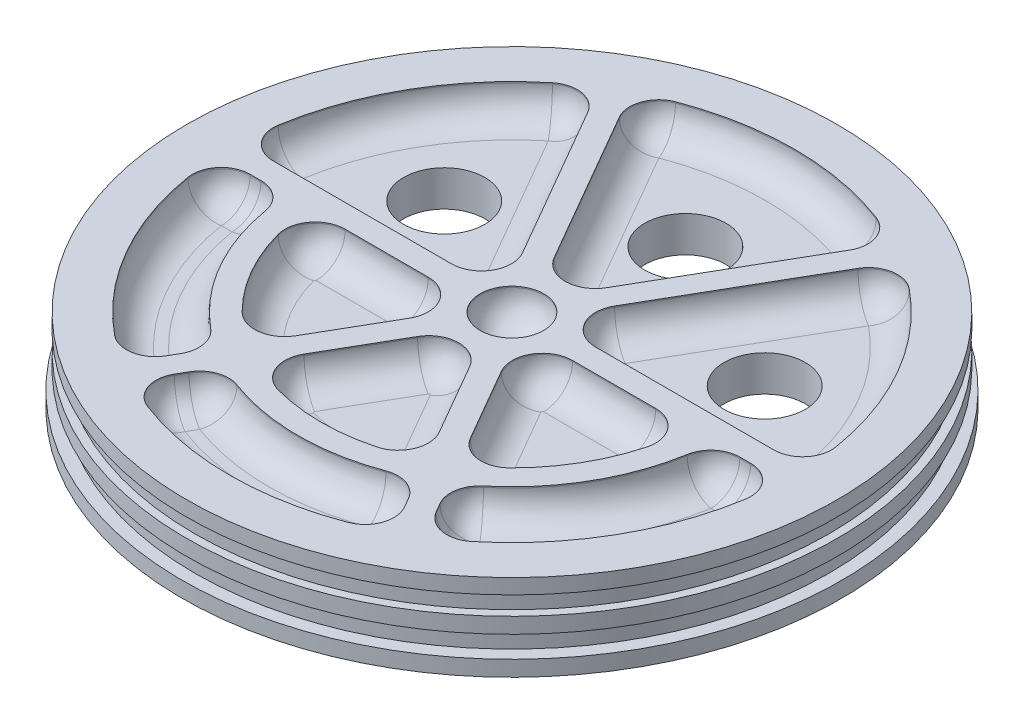
SolidWorks part; units mm, degrees
material "6061-T6 (SS)"
ref_plane "Front Plane" through (0, 0, 0) normal (0, 0, 1) x (1, 0, 0)
ref_plane "Top Plane" through (0, 0, 0) normal (0, 1, 0) x (1, 0, 0)
ref_plane "Right Plane" through (0, 0, 0) normal (1, 0, 0) x (0, 0, -1)
sketch "Sketch1" plane through (0, 0, 0) normal (0, 0, 1) x (1, 0, 0)
  line L0 (0, 48.1922) -> (0, -25.6743) construction
  line L1 (0, 0) -> (72.39, 0)
  line L2 (72.39, 0) -> (72.39, 3.429)
  line L3 (72.39, 3.429) -> (69.6468, 3.429)
  line L4 (69.6468, 3.429) -> (69.6468, 7.493)
  line L5 (69.6468, 7.493) -> (71.4248, 7.493)
  line L6 (71.4248, 7.493) -> (71.4248, 10.922)
  line L7 (71.4248, 10.922) -> (69.6468, 10.922)
  line L8 (62.0268, 18.288) -> (62.0268, 11.684)
  line L9 (62.0268, 11.684) -> (0, 11.684)
  line L10 (0, 11.684) -> (0, 0)
  line L11 (69.6468, 10.922) -> (69.6468, 14.986)
  line L12 (69.6468, 14.986) -> (71.4248, 14.986)
  line L13 (71.4248, 14.986) -> (71.4248, 18.288)
  line L14 (71.4248, 18.288) -> (62.0268, 18.288)
  dimension "D2" = 4.064
  dimension "D5" = 11.684
  dimension "D7" = 4.064
  dimension "D3" = 3.302
  dimension "D4" = 3.429
  dimension "D8" = 7.62
  dimension "D9" = 6.604
  dimension "D1" = 72.39
  dimension "D10" = 1.778
  dimension "D6" = 69.6468
revolve "Revolve1" add sketch "Sketch1" angle 360 about L0
sketch "Sketch6" plane through (0, 0, 0) normal (0, -1, 0) x (1, 0, 0)
  circle A0 centre (0, 0) radius 66.04
  dimension "D1" = 132.08
extrude "Boss-Extrude1" add sketch "Sketch6" along normal blind 2.54
fillet "CNC ID Fillet" [suppressed] radius 0.4064
fillet "CNC OD Fillet" [suppressed] radius 0.127
chamfer "CNC Chamfers" [suppressed] distance 0.508 angle 65
hole_wizard "Pipe Tap Drill for 1/2 Tap - Fill Valve" positions "Sketch13" profile "Sketch14" hole size "1/2" standard "ANSI Inch" end condition through all
sketch "Sketch13" plane through (0, -2.54, 0) normal (0, -1, 0) x (-1, 0, 0)
  point P4 (0, 38.1)
  dimension "D1" = 38.1
sketch "Sketch14" plane through (0, -2.54, -38.1) normal (1, 0, 0) x (0, 0, -1)
  line L0 (0, 0) -> (0, 20.828)
  line L1 (0, 20.828) -> (8.9281, 20.828)
  line L2 (8.9281, 20.828) -> (8.9281, 0)
  line L5 (8.9281, 0) -> (0, 0)
  line L11 (0, -6.35) -> (0, 107.95) construction
  dimension "Thru Hole Dia." = 17.8562
  dimension "Thru Hole Depth" = 20.828
hole_wizard "Pipe Tap Drill for 1/4 Tap - Solenoid Valve" positions "Sketch15" profile "Sketch16" hole size "1/2" standard "ANSI Inch" end condition through all
sketch "Sketch15" plane through (0, -2.54, 0) normal (0, -1, 0) x (-1, 0, 0)
  line L2 (-35.1953, 20.32) -> (0, 0) construction
  line L4 (0, 0) -> (0, 38.1) construction
  point P4 (-35.1953, 20.32)
  dimension "D1" = 60
  dimension "D2" = 40.64
sketch "Sketch16" plane through (35.1953, -2.54, -20.32) normal (1, 0, 0) x (0, 0, -1)
  line L0 (0, 0) -> (0, 20.828)
  line L1 (0, 20.828) -> (8.9281, 20.828)
  line L2 (8.9281, 20.828) -> (8.9281, 0)
  line L5 (8.9281, 0) -> (0, 0)
  line L11 (0, -6.35) -> (0, 107.95) construction
  dimension "Thru Hole Dia." = 17.8562
  dimension "Thru Hole Depth" = 20.828
hole_wizard "Pipe Tap Drill for 1/2 Tap - Cryo Valve" positions "Sketch17" profile "Sketch18" hole size "1/2" standard "ANSI Inch" end condition through all
sketch "Sketch17" plane through (0, -2.54, 0) normal (0, -1, 0) x (-1, 0, 0)
  line L2 (35.1953, 20.32) -> (0, 0) construction
  line L5 (0, 0) -> (0, 38.1) construction
  point P4 (35.1953, 20.32)
  dimension "D1" = 60
  dimension "D2" = 40.64
sketch "Sketch18" plane through (-35.1953, -2.54, -20.32) normal (1, 0, 0) x (0, 0, -1)
  line L0 (0, 0) -> (0, 20.828)
  line L1 (0, 20.828) -> (8.9281, 20.828)
  line L2 (8.9281, 20.828) -> (8.9281, 0)
  line L5 (8.9281, 0) -> (0, 0)
  line L11 (0, -6.35) -> (0, 107.95) construction
  dimension "Thru Hole Dia." = 17.8562
  dimension "Thru Hole Depth" = 20.828
sketch "Sketch19" plane through (0, 18.288, 0) normal (0, 1, 0) x (1, 0, 0)
  line L0 (0, 0) -> (31.0134, 53.7168) construction
  line L1 (0, 0) -> (-31.0134, 53.7168) construction
  line L2 (0, 0) -> (62.0268, 0) construction
  line L3 (0, 0) -> (0, 38.1) construction
  line L4 (0, 0) -> (31.0134, -53.7168) construction
  line L5 (0, 0) -> (-31.0134, -53.7168) construction
  line L6 (0, 0) -> (-62.0268, 0) construction
  line L7 (-5.7192, 14.986) -> (-28.8137, 54.9868)
  line L8 (-15.8379, 2.54) -> (-62.0268, 2.54)
  line L9 (-10.1186, -12.446) -> (-19.2504, -28.2626)
  line L10 (5.7192, -14.986) -> (14.851, -30.8026)
  line L11 (15.8379, -2.54) -> (34.1013, -2.54)
  line L12 (10.1186, 12.446) -> (33.2131, 52.4468)
  line L13 (-10.1186, 12.446) -> (-33.2131, 52.4468)
  line L14 (-15.8379, -2.54) -> (-34.1013, -2.54)
  line L15 (-5.7192, -14.986) -> (-14.851, -30.8026)
  line L16 (10.1186, -12.446) -> (23.1162, -34.9584)
  line L17 (15.8379, 2.54) -> (62.0268, 2.54)
  line L18 (5.7192, 14.986) -> (28.8137, 54.9868)
  line L19 (0, -2.54) -> (-62.0268, -2.54) construction
  line L20 (-2.1997, 1.27) -> (-33.2131, -52.4468) construction
  line L21 (-2.1997, -1.27) -> (28.8137, -54.9868) construction
  line L22 (2.1997, -1.27) -> (-28.8137, -54.9868) construction
  line L23 (2.1997, 1.27) -> (33.2131, -52.4468) construction
  line L24 (0, -2.54) -> (62.0268, -2.54) construction
  line L25 (0, 2.54) -> (62.0268, 2.54) construction
  line L26 (2.1997, -1.27) -> (33.2131, 52.4468) construction
  line L27 (-2.1997, 1.27) -> (28.8137, 54.9868) construction
  line L28 (2.1997, 1.27) -> (-28.8137, 54.9868) construction
  line L29 (0, 2.54) -> (-62.0268, 2.54) construction
  line L30 (-2.1997, -1.27) -> (-33.2131, 52.4468) construction
  line L31 (-46.9213, -2.54) -> (-62.0268, -2.54)
  line L32 (46.9213, -2.54) -> (62.0268, -2.54)
  line L35 (-25.6604, -39.365) -> (-33.2131, -52.4468)
  line L36 (-21.2609, -41.905) -> (-28.8137, -54.9868)
  line L37 (21.2609, -41.905) -> (28.8137, -54.9868)
  line L38 (25.6604, -39.365) -> (33.2131, -52.4468)
  circle A0 centre (0, 0) radius 6.985
  circle A2 centre (0, 0) radius 62.0268
  arc A6 (-15.8379, -2.54) -> (-10.1186, -12.446) centre (-15.8379, -9.144) cw
  arc A7 (5.7192, -14.986) -> (-5.7192, -14.986) centre (0, -18.288) ccw
  arc A8 (10.1186, -12.446) -> (15.8379, -2.54) centre (15.8379, -9.144) cw
  arc A9 (15.8379, 2.54) -> (10.1186, 12.446) centre (15.8379, 9.144) cw
  arc A10 (5.7192, 14.986) -> (-5.7192, 14.986) centre (0, 18.288) cw
  arc A11 (-15.8379, 2.54) -> (-10.1186, 12.446) centre (-15.8379, 9.144) ccw
  arc A12 (-44.3774, -2.54) -> (44.3774, -2.54) centre (0, 0) ccw construction
  arc A13 (-46.9213, -2.54) -> (-25.6604, -39.365) centre (0, 0) ccw
  arc A14 (-40.48, -10.8544) -> (-29.6402, -29.6295) centre (0, 0) ccw
  arc A15 (-41.91, 0) -> (41.91, 0) centre (0, 0) ccw construction
  arc A16 (-44.45, 0) -> (44.45, 0) centre (0, 0) ccw construction
  arc A17 (-46.99, 0) -> (46.99, 0) centre (0, 0) ccw construction
  arc A19 (-10.8398, -40.4839) -> (10.8398, -40.4839) centre (0, 0) ccw
  arc A20 (23.1162, -34.9584) -> (40.48, -10.8544) centre (0, 0) ccw
  arc A21 (-21.2609, -41.905) -> (21.2609, -41.905) centre (0, 0) ccw
  arc A22 (25.6604, -39.365) -> (46.9213, -2.54) centre (0, 0) ccw
  arc A23 (-40.48, -10.8544) -> (-34.1013, -2.54) centre (-34.1013, -9.144) cw
  arc A24 (34.1013, -2.54) -> (40.48, -10.8544) centre (34.1013, -9.144) cw
  arc A25 (14.851, -30.8026) -> (10.8398, -40.4839) centre (9.1317, -34.1046) cw
  arc A26 (-10.8398, -40.4839) -> (-14.851, -30.8026) centre (-9.1317, -34.1046) cw
  arc A27 (-29.6402, -29.6295) -> (-19.2504, -28.2626) centre (-24.9696, -24.9606) ccw
  circle A28 centre (0, 0) radius 62.0268 construction
  point P12 (0, 0)
  point P13 (0, 0)
  dimension "D1" = 30
  dimension "D5" = 6.604
  dimension "D8" = 44.45
  dimension "D9" = 6.604
  dimension "D10" = 13.97
  dimension "D2" = 6
  dimension "D3" = 2.54
  dimension "D4" = 2.54
  dimension "D6" = 2.54
  dimension "D7" = 2.54
extrude "Boss-Extrude2" add sketch "Sketch19" against normal up to next contours A11 L8 L14 A6 L9 L15 A7 L10 L16 A8 L11 L17 A9 L12 L18 A10 L7 L13 region at (-0.1345, 18.288, 7.7292)
fillet "Fillet2" radius 6.35 61 edges at (-38.9063, 11.684, -2.54) (-10.1186, 11.684, -5.842) (-17.2535, 11.684, -34.9639) (0, 11.684, -11.684) (38.9063, 11.684, -2.54) (10.1186, 11.684, -5.842) (16.6174, 11.684, 23.7022) (10.1186, 11.684, 5.842) (24.9696, 11.684, 2.54) (-10.2851, 11.684, 22.8943) (0, 11.684, 11.684) (10.2851, 11.684, 22.8943) (-24.9696, 11.684, 2.54) (-10.1186, 11.684, 5.842) (-14.6845, 11.684, 20.3543) (-21.6529, 11.684, -32.4239) (17.2535, 11.684, -34.9639) (21.6529, 11.684, -32.4239) (34.0054, 11.684, 24.4965) (0, 11.684, 41.91) (-36.2951, 11.684, 20.955) (39.341, 11.684, 5.1242) (-15.2328, 11.684, 36.6324) (15.2328, 11.684, 36.6324) (-39.341, 11.684, 5.1242) (-24.1082, 11.684, 31.5082) (29.4237, 11.684, 45.8834) (40.6945, 11.684, 23.495) (54.448, 11.684, 2.54) (-25.0243, 11.684, 48.4234) (0, 11.684, 46.99) (25.0243, 11.684, 48.4234) (-54.448, 11.684, 2.54) (-40.6945, 11.684, 23.495) (-29.4237, 11.684, 45.8834) (46.9213, 14.986, 2.54) (25.6604, 14.986, 39.365) (21.2609, 14.986, 41.905) (-21.2609, 14.986, 41.905) (-25.6604, 14.986, 39.365) (-46.9213, 14.986, 2.54) (33.1871, 14.986, 52.4017) (61.9748, 14.986, 2.54) (-28.7877, 14.986, 54.9417) (28.7877, 14.986, 54.9417) (-61.9748, 14.986, 2.54) (-33.1871, 14.986, 52.4017) (-61.9748, 14.986, -2.54) (-33.1871, 14.986, -52.4017) (-28.7877, 14.986, -54.9417) (28.7877, 14.986, -54.9417) (61.9748, 14.986, -2.54) (33.1871, 14.986, -52.4017) (53.7168, 11.684, 31.0134) (0, 11.684, 62.0268) (-53.7168, 11.684, 31.0134) (-53.7168, 11.684, -31.0134) (53.7168, 11.684, -31.0134) (0, 11.684, -62.0268) (6.985, 11.684, 0) (23.1162, 14.986, 34.9584)
sketch "Sketch21" plane through (0, 18.288, 0) normal (0, 1, 0) x (1, 0, 0)
  circle A0 centre (0, 0) radius 66.3169 construction
  text T0 "                                                                                                                                                           RELEVANT EXPERIENCE"
sketch "Sketch22" plane through (0, -2.54, 0) normal (0, -1, 0) x (1, 0, 0)
  line L39 (-29.6809, -46.3289) -> (-10.1186, -12.446)
  line L59 (-15.8379, -2.54) -> (-54.9625, -2.54)
  line L74 (-29.6809, -46.3289) -> (-10.1186, -12.446)
  line L78 (-15.8379, -2.54) -> (-54.9625, -2.54)
  line L82 (-34.1013, 2.54) -> (-15.8379, 2.54)
  line L86 (-10.1186, 12.446) -> (-19.2504, 28.2626)
  line L90 (-34.1013, 2.54) -> (-15.8379, 2.54)
  line L94 (-10.1186, 12.446) -> (-19.2504, 28.2626)
  line L98 (15.8379, 2.54) -> (34.1013, 2.54)
  line L101 (19.4151, 28.548) -> (10.1186, 12.446)
  line L102 (15.8379, 2.54) -> (34.1013, 2.54)
  line L103 (19.4151, 28.548) -> (10.1186, 12.446)
  line L104 (-14.851, 30.8026) -> (-5.7192, 14.986)
  line L105 (5.7192, 14.986) -> (14.851, 30.8026)
  line L106 (-14.851, 30.8026) -> (-5.7192, 14.986)
  line L107 (5.7192, 14.986) -> (14.851, 30.8026)
  line L108 (-28.4967, 44.2777) -> (-29.6809, 46.3289)
  line L109 (-54.9625, 2.54) -> (-52.5939, 2.54)
  line L110 (-28.4967, 44.2777) -> (-29.6809, 46.3289)
  line L111 (-54.9625, 2.54) -> (-52.5939, 2.54)
  line L112 (24.0973, 46.8177) -> (25.2815, 48.8689)
  line L113 (-25.2815, 48.8689) -> (-24.0973, 46.8177)
  line L114 (24.0973, 46.8177) -> (25.2815, 48.8689)
  line L115 (-25.2815, 48.8689) -> (-24.0973, 46.8177)
  line L116 (52.5939, 2.54) -> (54.9625, 2.54)
  line L117 (29.6809, 46.3289) -> (28.4967, 44.2777)
  line L118 (52.5939, 2.54) -> (54.9625, 2.54)
  line L119 (29.6809, 46.3289) -> (28.4967, 44.2777)
  line L120 (10.1186, -12.446) -> (29.6809, -46.3289)
  line L121 (54.9625, -2.54) -> (15.8379, -2.54)
  line L122 (10.1186, -12.446) -> (29.6809, -46.3289)
  line L123 (54.9625, -2.54) -> (15.8379, -2.54)
  line L124 (-5.7192, -14.986) -> (-25.2815, -48.8689)
  line L125 (25.2815, -48.8689) -> (5.7192, -14.986)
  line L126 (-5.7192, -14.986) -> (-25.2815, -48.8689)
  line L127 (25.2815, -48.8689) -> (5.7192, -14.986)
  circle A3 centre (0, 0) radius 6.985
  circle A93 centre (0, 0) radius 6.985
  arc A205 (-61.231, -9.9039) -> (-39.1925, -48.0757) centre (0, 0) ccw
  arc A214 (-39.1925, -48.0757) -> (-29.6809, -46.3289) centre (-35.1802, -43.1539) ccw
  arc A217 (-10.1186, -12.446) -> (-15.8379, -2.54) centre (-15.8379, -9.144) ccw
  arc A229 (-54.9625, -2.54) -> (-61.231, -9.9039) centre (-54.9625, -8.89) ccw
  arc A241 (-61.231, -9.9039) -> (-39.1925, -48.0757) centre (0, 0) ccw
  arc A267 (-39.1925, -48.0757) -> (-29.6809, -46.3289) centre (-35.1802, -43.1539) ccw
  arc A268 (-10.1186, -12.446) -> (-15.8379, -2.54) centre (-15.8379, -9.144) ccw
  arc A269 (-54.9625, -2.54) -> (-61.231, -9.9039) centre (-54.9625, -8.89) ccw
  arc A270 (-19.2504, 28.2626) -> (-29.6402, 29.6295) centre (-24.9696, 24.9606) ccw
  arc A271 (-29.6402, 29.6295) -> (-40.48, 10.8544) centre (0, 0) ccw
  arc A272 (-40.48, 10.8544) -> (-34.1013, 2.54) centre (-34.1013, 9.144) ccw
  arc A273 (-15.8379, 2.54) -> (-10.1186, 12.446) centre (-15.8379, 9.144) ccw
  arc A274 (-19.2504, 28.2626) -> (-29.6402, 29.6295) centre (-24.9696, 24.9606) ccw
  arc A275 (-29.6402, 29.6295) -> (-40.48, 10.8544) centre (0, 0) ccw
  arc A276 (-40.48, 10.8544) -> (-34.1013, 2.54) centre (-34.1013, 9.144) ccw
  arc A277 (-15.8379, 2.54) -> (-10.1186, 12.446) centre (-15.8379, 9.144) ccw
  arc A278 (34.1013, 2.54) -> (40.48, 10.8544) centre (34.1013, 9.144) ccw
  arc A279 (40.48, 10.8544) -> (29.3634, 29.9039) centre (0, 0) ccw
  arc A280 (29.3634, 29.9039) -> (19.4151, 28.548) centre (24.9144, 25.373) ccw
  arc A281 (10.1186, 12.446) -> (15.8379, 2.54) centre (15.8379, 9.144) ccw
  arc A282 (34.1013, 2.54) -> (40.48, 10.8544) centre (34.1013, 9.144) ccw
  arc A283 (40.48, 10.8544) -> (29.3634, 29.9039) centre (0, 0) ccw
  arc A284 (29.3634, 29.9039) -> (19.4151, 28.548) centre (24.9144, 25.373) ccw
  arc A285 (10.1186, 12.446) -> (15.8379, 2.54) centre (15.8379, 9.144) ccw
  arc A286 (10.8398, 40.4839) -> (-10.8398, 40.4839) centre (0, 0) ccw
  arc A287 (-10.8398, 40.4839) -> (-14.851, 30.8026) centre (-9.1317, 34.1046) ccw
  arc A288 (-5.7192, 14.986) -> (5.7192, 14.986) centre (0, 18.288) ccw
  arc A289 (14.851, 30.8026) -> (10.8398, 40.4839) centre (9.1317, 34.1046) ccw
  arc A290 (10.8398, 40.4839) -> (-10.8398, 40.4839) centre (0, 0) ccw
  arc A291 (-10.8398, 40.4839) -> (-14.851, 30.8026) centre (-9.1317, 34.1046) ccw
  arc A292 (-5.7192, 14.986) -> (5.7192, 14.986) centre (0, 18.288) ccw
  arc A293 (14.851, 30.8026) -> (10.8398, 40.4839) centre (9.1317, 34.1046) ccw
  arc A296 (29.6809, -46.3289) -> (39.1925, -48.0757) centre (35.1802, -43.1539) ccw
  arc A297 (39.1925, -48.0757) -> (61.231, -9.9039) centre (0, 0) ccw
  arc A298 (-29.9488, 36.2095) -> (-46.3328, 7.8317) centre (0, 0) ccw
  arc A299 (-29.9488, 36.2095) -> (-28.4967, 44.2777) centre (-33.9959, 41.1027) ccw
  arc A300 (-29.6809, 46.3289) -> (-39.1925, 48.0757) centre (-35.1802, 43.1539) ccw
  arc A301 (-39.1925, 48.0757) -> (-61.231, 9.9039) centre (0, 0) ccw
  arc A302 (-61.231, 9.9039) -> (-54.9625, 2.54) centre (-54.9625, 8.89) ccw
  arc A303 (-52.5939, 2.54) -> (-46.3328, 7.8317) centre (-52.5939, 8.89) ccw
  arc A304 (-29.9488, 36.2095) -> (-46.3328, 7.8317) centre (0, 0) ccw
  arc A305 (-29.9488, 36.2095) -> (-28.4967, 44.2777) centre (-33.9959, 41.1027) ccw
  arc A306 (-29.6809, 46.3289) -> (-39.1925, 48.0757) centre (-35.1802, 43.1539) ccw
  arc A307 (-39.1925, 48.0757) -> (-61.231, 9.9039) centre (0, 0) ccw
  arc A308 (-61.231, 9.9039) -> (-54.9625, 2.54) centre (-54.9625, 8.89) ccw
  arc A309 (-52.5939, 2.54) -> (-46.3328, 7.8317) centre (-52.5939, 8.89) ccw
  arc A310 (16.384, 44.0412) -> (-16.384, 44.0412) centre (0, 0) ccw
  arc A311 (16.384, 44.0412) -> (24.0973, 46.8177) centre (18.598, 49.9927) ccw
  arc A312 (25.2815, 48.8689) -> (22.0385, 57.9796) centre (19.7823, 52.0439) ccw
  arc A313 (22.0385, 57.9796) -> (-22.0385, 57.9796) centre (0, 0) ccw
  arc A314 (-22.0385, 57.9796) -> (-25.2815, 48.8689) centre (-19.7823, 52.0439) ccw
  arc A315 (-24.0973, 46.8177) -> (-16.384, 44.0412) centre (-18.598, 49.9927) ccw
  arc A316 (16.384, 44.0412) -> (-16.384, 44.0412) centre (0, 0) ccw
  arc A317 (16.384, 44.0412) -> (24.0973, 46.8177) centre (18.598, 49.9927) ccw
  arc A318 (25.2815, 48.8689) -> (22.0385, 57.9796) centre (19.7823, 52.0439) ccw
  arc A319 (22.0385, 57.9796) -> (-22.0385, 57.9796) centre (0, 0) ccw
  arc A320 (-22.0385, 57.9796) -> (-25.2815, 48.8689) centre (-19.7823, 52.0439) ccw
  arc A321 (-24.0973, 46.8177) -> (-16.384, 44.0412) centre (-18.598, 49.9927) ccw
  arc A322 (46.3328, 7.8317) -> (29.9488, 36.2095) centre (0, 0) ccw
  arc A323 (46.3328, 7.8317) -> (52.5939, 2.54) centre (52.5939, 8.89) ccw
  arc A324 (54.9625, 2.54) -> (61.231, 9.9039) centre (54.9625, 8.89) ccw
  arc A325 (61.231, 9.9039) -> (39.1925, 48.0757) centre (0, 0) ccw
  arc A326 (39.1925, 48.0757) -> (29.6809, 46.3289) centre (35.1802, 43.1539) ccw
  arc A327 (28.4967, 44.2777) -> (29.9488, 36.2095) centre (33.9959, 41.1027) ccw
  arc A328 (46.3328, 7.8317) -> (29.9488, 36.2095) centre (0, 0) ccw
  arc A329 (46.3328, 7.8317) -> (52.5939, 2.54) centre (52.5939, 8.89) ccw
  arc A330 (54.9625, 2.54) -> (61.231, 9.9039) centre (54.9625, 8.89) ccw
  arc A331 (61.231, 9.9039) -> (39.1925, 48.0757) centre (0, 0) ccw
  arc A332 (39.1925, 48.0757) -> (29.6809, 46.3289) centre (35.1802, 43.1539) ccw
  arc A333 (28.4967, 44.2777) -> (29.9488, 36.2095) centre (33.9959, 41.1027) ccw
  arc A334 (61.231, -9.9039) -> (54.9625, -2.54) centre (54.9625, -8.89) ccw
  arc A335 (15.8379, -2.54) -> (10.1186, -12.446) centre (15.8379, -9.144) ccw
  arc A336 (29.6809, -46.3289) -> (39.1925, -48.0757) centre (35.1802, -43.1539) ccw
  arc A337 (39.1925, -48.0757) -> (61.231, -9.9039) centre (0, 0) ccw
  arc A338 (61.231, -9.9039) -> (54.9625, -2.54) centre (54.9625, -8.89) ccw
  arc A339 (15.8379, -2.54) -> (10.1186, -12.446) centre (15.8379, -9.144) ccw
  arc A340 (-25.2815, -48.8689) -> (-22.0385, -57.9796) centre (-19.7823, -52.0439) ccw
  arc A341 (-22.0385, -57.9796) -> (22.0385, -57.9796) centre (0, 0) ccw
  arc A342 (22.0385, -57.9796) -> (25.2815, -48.8689) centre (19.7823, -52.0439) ccw
  arc A343 (5.7192, -14.986) -> (-5.7192, -14.986) centre (0, -18.288) ccw
  arc A344 (-25.2815, -48.8689) -> (-22.0385, -57.9796) centre (-19.7823, -52.0439) ccw
  arc A345 (-22.0385, -57.9796) -> (22.0385, -57.9796) centre (0, 0) ccw
  arc A346 (22.0385, -57.9796) -> (25.2815, -48.8689) centre (19.7823, -52.0439) ccw
  arc A347 (5.7192, -14.986) -> (-5.7192, -14.986) centre (0, -18.288) ccw
  circle M63 centre (-35.1953, -20.32) radius 8.9281
  circle M64 centre (35.1953, -20.32) radius 8.9281
  circle M65 centre (0, -38.1) radius 8.9281
  dimension "D1" = 0
  dimension "D2" = 0
  dimension "D3" = 0
  dimension "D4" = 0
  dimension "D5" = 0
  dimension "D6" = 0
  dimension "D7" = 0
  dimension "D8" = 0
  dimension "D9" = 0
  dimension "D10" = 0
extrude "Cut-Extrude1" cut sketch "Sketch22" against normal blind 6.35 contours M64 | M65 | M63 | A93 | L102 A282 A283 A284 L103 A285 | A290 A291 L106 A292 L107 A293 | A274 A275 A276 L90 A277 L94 | A304 A309 L111 A308 A307 A306 L110 A305 | A316 A321 L115 A320 A319 A318 L114 A317 | A328 A333 L119 A332 A331 A330 L118 A329 region at (-34.1599, -2.54, -48.7097) region at (10.726, -2.54, -6.1926) region at (0, -2.54, -12.4097)
fillet "Fillet3" radius 6.35 61 edges at (59.7978, 3.81, -4.7739) (53.7168, 3.81, -31.0134) (34.0332, 3.81, -49.3995) (19.8998, 3.81, -29.3875) (10.1186, 3.81, -5.842) (-10.1186, 3.81, -5.842) (-19.8998, 3.81, -29.3875) (-34.0332, 3.81, -49.3995) (-53.7168, 3.81, -31.0134) (-59.7978, 3.81, -4.7739) (0, 3.81, -11.684) (15.5004, 3.81, -31.9275) (25.7646, 3.81, -54.1734) (0, 3.81, -62.0268) (-25.7646, 3.81, -54.1734) (-40.6945, 3.81, 23.495) (-48.495, 3.81, 4.0401) (-53.7782, 3.81, 2.54) (-59.7978, 3.81, 4.7739) (-53.7168, 3.81, 31.0134) (-34.0332, 3.81, 49.3995) (-29.0888, 3.81, 45.3033) (-27.7464, 3.81, 39.9779) (0, 3.81, 46.99) (-20.7487, 3.81, 44.018) (-24.6894, 3.81, 47.8433) (-25.7646, 3.81, 54.1734) (0, 3.81, 62.0268) (25.7646, 3.81, 54.1734) (24.6894, 3.81, 47.8433) (20.7487, 3.81, 44.018) (40.6945, 3.81, 23.495) (27.7464, 3.81, 39.9779) (29.0888, 3.81, 45.3033) (34.0332, 3.81, 49.3995) (53.7168, 3.81, 31.0134) (59.7978, 3.81, 4.7739) (53.7782, 3.81, 2.54) (48.495, 3.81, 4.0401) (14.7669, 3.81, 20.497) (24.0568, 3.81, 31.6648) (36.1973, 3.81, 21.1235) (39.341, 3.81, 5.1242) (24.9696, 3.81, 2.54) (10.1186, 3.81, 5.842) (10.2851, 3.81, 22.8943) (0, 3.81, 11.684) (-10.2851, 3.81, 22.8943) (-15.2328, 3.81, 36.6324) (0, 3.81, 41.91) (15.2328, 3.81, 36.6324) (-10.1186, 3.81, 5.842) (-24.9696, 3.81, 2.54) (-39.341, 3.81, 5.1242) (-36.2951, 3.81, 20.955) (-24.1082, 3.81, 31.5082) (-14.6845, 3.81, 20.3543) (6.985, 3.81, 0) (35.4002, 3.81, -2.54) (-35.4002, 3.81, -2.54) (-15.5004, 3.81, -31.9275)
sketch "Sketch20" plane through (0, 3.81, 0) normal (0, -1, 0) x (-1, 0, 0)
  line L0 (0, 0) -> (-35.1953, 20.32) construction
  line L1 (-40.2753, 11.5212) -> (-30.1153, 29.1188) construction
  line L2 (-11.43, 38.1) -> (11.43, 38.1) construction
  line L3 (0, 0) -> (0, 38.1) construction
  line L4 (40.2753, 11.5212) -> (30.1153, 29.1188) construction
  line L5 (0, 0) -> (35.1953, 20.32) construction
  arc A1 (11.43, 38.1) -> (-11.43, 38.1) centre (0, 38.1) ccw construction
  arc A2 (11.43, 38.1) -> (-11.43, 38.1) centre (0, 38.1) cw construction
  arc A3 (-40.2753, 11.5212) -> (-30.1153, 29.1188) centre (-35.1953, 20.32) ccw construction
  arc A4 (-40.2753, 11.5212) -> (-30.1153, 29.1188) centre (-35.1953, 20.32) cw construction
  arc A5 (40.2753, 11.5212) -> (30.1153, 29.1188) centre (35.1953, 20.32) ccw construction
  arc A6 (40.2753, 11.5212) -> (30.1153, 29.1188) centre (35.1953, 20.32) cw construction
  text T1 "FILL" font "Century Gothic" height in points 20
  text T3 "INJECTOR" font "Century Gothic" height in points 12
  text T4 "DUMP" font "Century Gothic" height in points 14
  point P14 (-35.1953, 20.32)
  dimension "D1" = 11.43
  dimension "D2" = 10.16
sketch "Sketch24" plane through (0, -2.54, 0) normal (0, -1, 0) x (1, 0, 0)
  arc A0 (-42.672, 0) -> (42.672, 0) centre (0, 0) cw construction
  text T0 "THIS SIDE OUT" font "Century Gothic" height in points 12
  dimension "D1" = 42.672
equation "\"D6@Sketch1\"=5.484/2"
equation "\"D1@Sketch1\"=5.7/2"
